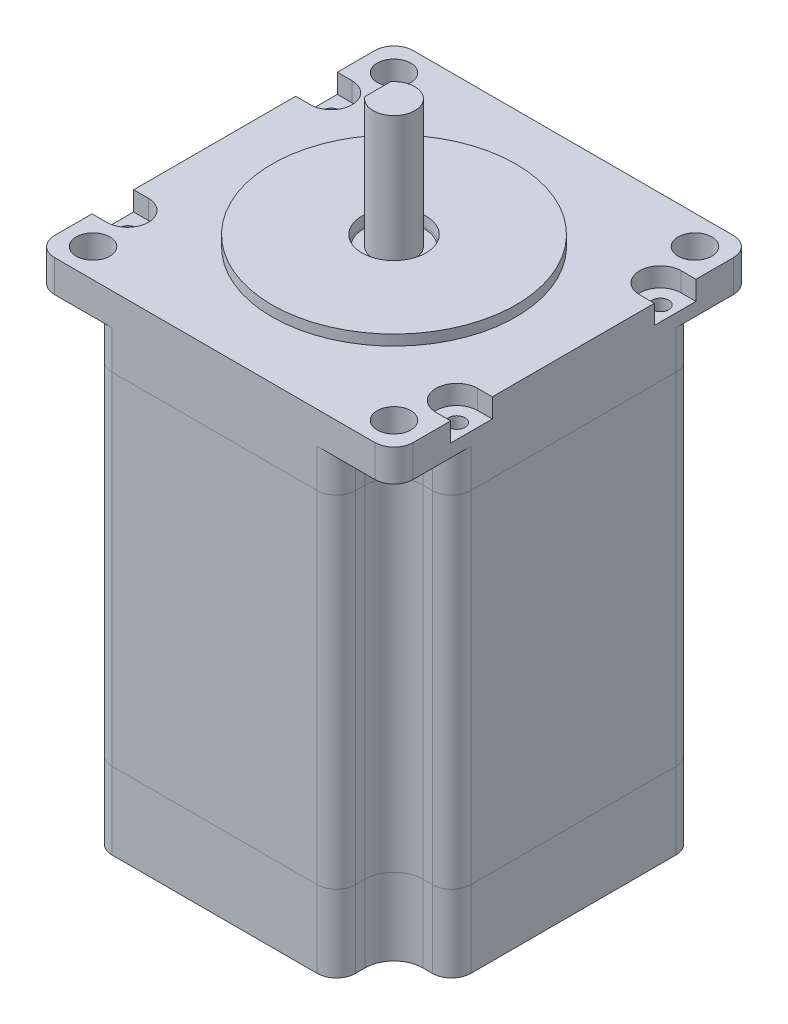
SolidWorks part; units mm, degrees
ref_plane "Front Plane" through (0, 0, 0) normal (0, 0, 1) x (1, 0, 0)
ref_plane "Top Plane" through (0, 0, 0) normal (0, 1, 0) x (1, 0, 0)
ref_plane "Right Plane" through (0, 0, 0) normal (1, 0, 0) x (0, 0, -1)
sketch "Sketch2" plane through (0, 0, 0) normal (0, 1, 0) x (1, 0, 0)
  line L0 (-28, 0) -> (28, 0) construction
  line L1 (0, -28) -> (0, 28) construction
  line L2 (-16, 28) -> (16, 28)
  line L3 (-28, -16) -> (-28, 16)
  line L4 (28, -16) -> (28, 16)
  line L5 (-16, -28) -> (16, -28)
  line L10 (-25, 19) -> (-23.4993, 19)
  line L11 (-19, 25) -> (-19, 23.4993)
  line L12 (-19, 23.4993) -> (-18.9317, 23.4767)
  line L13 (19, 25) -> (19, 23.4993)
  line L14 (25, 19) -> (23.4993, 19)
  line L15 (-19, -23.4993) -> (-18.9317, -23.4767)
  line L16 (-19, -25) -> (-19, -23.4993)
  line L17 (-25, -19) -> (-23.4993, -19)
  line L18 (25, -19) -> (23.4993, -19)
  line L19 (19, -25) -> (19, -23.4993)
  circle A0 centre (-25.7, 15.9) radius 1.3
  arc A1 (-19, 23.4993) -> (-23.4993, 19) centre (-23.4993, 23.4993) cw
  arc A2 (-28, 16) -> (-25, 19) centre (-25, 16) cw
  arc A3 (-16, 28) -> (-19, 25) centre (-16, 25) ccw
  arc A4 (16, 28) -> (19, 25) centre (16, 25) cw
  arc A5 (19, 23.4993) -> (23.4993, 19) centre (23.4993, 23.4993) ccw
  arc A6 (28, 16) -> (25, 19) centre (25, 16) ccw
  circle A7 centre (25.7, 15.9) radius 1.3
  arc A8 (-16, -28) -> (-19, -25) centre (-16, -25) cw
  arc A9 (-28, -16) -> (-25, -19) centre (-25, -16) ccw
  arc A10 (-19, -23.4993) -> (-23.4993, -19) centre (-23.4993, -23.4993) ccw
  circle A11 centre (-25.7, -15.9) radius 1.3
  circle A12 centre (25.7, -15.9) radius 1.3
  arc A13 (28, -16) -> (25, -19) centre (25, -16) cw
  arc A14 (19, -23.4993) -> (23.4993, -19) centre (23.4993, -23.4993) cw
  arc A15 (16, -28) -> (19, -25) centre (16, -25) ccw
  circle A16 centre (0, 0) radius 5
  point P3 (0, 0)
  point P6 (0, 0)
  point P9 (0, 28)
  point P12 (-28, 0)
  point P15 (28, 0)
  point P18 (0, -28)
  point P25 (-23.4993, 23.4993)
  dimension "D5" = 2.6
  dimension "D8" = 3
  dimension "D9" = 10
  dimension "D1" = 56
  dimension "D2" = 56
extrude "Boss-Extrude2" add sketch "Sketch2" along normal blind 12 contours L5 A15 L19 A14 L18 A13 L4 A6 L14 A5 L13 A4 L2 A3 L11 A1 L10 A2 L3 A9 L17 A10 L16 A8 A16 A11 A0 A7 A12 region at (0, 0, -27.208)
extrude "Boss-Extrude3" add sketch "Sketch2<5>" along normal blind 53.3 from surface separate body contours L5 A15 L19 A14 L18 A13 L4 A6 L14 A5 L13 A4 L2 A3 L11 A1 L10 A2 L3 A9 L17 A10 L16 A8 A16 A11 A0 A7 A12 region at (0, 0, -27.208) starting at face at (0, 12, 5)
sketch "Sketch2<5>" plane through (0, 0, 0) normal (0, 1, 0) x (1, 0, 0) same geometry as "Sketch2"
extrude "Boss-Extrude4" add sketch "Sketch2<6>" along normal blind 6 from surface separate body contours L5 A15 L19 A14 L18 A13 L4 A6 L14 A5 L13 A4 L2 A3 L11 A1 L10 A2 L3 A9 L17 A10 L16 A8 A16 A11 A0 A7 A12 region at (0, 0, -27.208) starting at face at (-25.7, 65.3, -14.6)
sketch "Sketch2<6>" plane through (0, 0, 0) normal (0, 1, 0) x (1, 0, 0) same geometry as "Sketch2"
ref_plane "Plane1" through (0, 71.3, 0) normal (0, 1, 0) x (1, 0, 0)
sketch "Sketch4" plane through (0, 71.3, 0) normal (0, 1, 0) x (1, 0, 0)
  line L0 (-28, 0) -> (28, 0) construction
  line L1 (0, -28) -> (0, 28) construction
  line L2 (-28, 28) -> (28, 28)
  line L3 (-28, -28) -> (-28, -19.15)
  line L4 (28, -28) -> (28, -19.15)
  line L5 (-28, -28) -> (28, -28)
  line L6 (25.7, 19.15) -> (28, 19.15)
  line L7 (25.7, 12.65) -> (28, 12.65)
  line L8 (-25.7, 19.15) -> (-28, 19.15)
  line L9 (-25.7, 12.65) -> (-28, 12.65)
  line L10 (28, 19.15) -> (28, 28)
  line L11 (25.7, -12.65) -> (28, -12.65)
  line L12 (25.7, -19.15) -> (28, -19.15)
  line L13 (-25.7, -19.15) -> (-28, -19.15)
  line L14 (-25.7, -12.65) -> (-28, -12.65)
  line L15 (-28, -12.65) -> (-28, 12.65)
  line L16 (28, -12.65) -> (28, 12.65)
  line L17 (-28, 19.15) -> (-28, 28)
  line L18 (-28, 19.15) -> (-28, 12.65)
  line L19 (-28, -12.65) -> (-28, -19.15)
  line L20 (28, -12.65) -> (28, -19.15)
  line L21 (28, 19.15) -> (28, 12.65)
  circle A0 centre (-25.7, 15.9) radius 1.3
  arc A1 (25.7, 19.15) -> (25.7, 12.65) centre (25.7, 15.9) ccw
  circle A2 centre (-23.4993, 23.4993) radius 2.625
  circle A3 centre (23.4993, 23.4993) radius 2.625
  circle A4 centre (-23.4993, -23.4993) radius 2.625
  circle A5 centre (23.4993, -23.4993) radius 2.625
  arc A6 (-25.7, 19.15) -> (-25.7, 12.65) centre (-25.7, 15.9) cw
  arc A7 (25.7, -19.15) -> (25.7, -12.65) centre (25.7, -15.9) cw
  arc A8 (-25.7, -19.15) -> (-25.7, -12.65) centre (-25.7, -15.9) ccw
  circle A9 centre (25.7, 15.9) radius 1.3
  circle A10 centre (25.7, -15.9) radius 1.3
  circle A11 centre (-25.7, -15.9) radius 1.3
  circle A16 centre (0, 0) radius 5
  point P2 (0, 0)
  point P5 (0, 0)
  point P8 (0, 28)
  point P11 (-28, 0)
  point P14 (28, 0)
  point P17 (0, -28)
  point P21 (-23.4993, 23.4993)
  dimension "D4" = 6.5
  dimension "D5" = 10
  dimension "D6" = 5.25
  dimension "D7" = 5.25
  dimension "D8" = 5.25
  dimension "D9" = 5.25
  dimension "D1" = 56
  dimension "D2" = 56
extrude "Boss-Extrude5" add sketch "Sketch4" along normal blind 5 contours A6 L8 L18 L9 | L6 A1 L7 L21 | A8 L13 L3 L5 L4 L12 A7 L11 L16 L7 A1 L6 L10 L2 L17 L8 A6 L9 L15 L14 A16 A5 A4 A3 A2 | L13 A8 L14 L19 | A7 L12 L20 L11 region at (0, 71.3, -27.208) region at (-26.85, 71.3, -19.0645) region at (27.9145, 71.3, -15.9) region at (-26.85, 71.3, 12.7355) region at (27.9145, 71.3, 15.9)
sketch "Sketch5" plane through (0, 71.3, 0) normal (0, 1, 0) x (1, 0, 0)
  line L0 (-28, 19.15) -> (-28, 12.65)
  line L1 (-28, 12.65) -> (-25.7, 12.65)
  line L2 (-25.7, 19.15) -> (-28, 19.15)
  line L3 (0, 28) -> (0, -28) construction
  line L4 (-28, 0) -> (28, 0) construction
  line L5 (25.7, 19.15) -> (28, 19.15)
  line L6 (28, 12.65) -> (25.7, 12.65)
  line L7 (28, 19.15) -> (28, 12.65)
  line L8 (28, -19.15) -> (28, -12.65)
  line L9 (28, -12.65) -> (25.7, -12.65)
  line L10 (25.7, -19.15) -> (28, -19.15)
  line L11 (-25.7, -19.15) -> (-28, -19.15)
  line L12 (-28, -12.65) -> (-25.7, -12.65)
  line L13 (-28, -19.15) -> (-28, -12.65)
  arc A0 (-25.7, 12.65) -> (-25.7, 19.15) centre (-25.7, 15.9) ccw
  arc A1 (25.7, 12.65) -> (25.7, 19.15) centre (25.7, 15.9) cw
  arc A2 (25.7, -12.65) -> (25.7, -19.15) centre (25.7, -15.9) ccw
  arc A3 (-25.7, -12.65) -> (-25.7, -19.15) centre (-25.7, -15.9) cw
extrude "Cut-Extrude1" cut sketch "Sketch5" against normal blind 3 from surface starting at face at (0, 76.3, 0)
ref_plane "Plane2" through (0, 76.3, 0) normal (0, 1, 0) x (1, 0, 0)
sketch "Sketch6" plane through (0, 76.3, 0) normal (0, 1, 0) x (1, 0, 0)
  line L1 (-2.55, -2.0149) -> (-2.55, 2.0149)
  arc A0 (-2.55, -2.0149) -> (-2.55, 2.0149) centre (0, 0) ccw
  point P8 (-2.55, 0)
  dimension "D1" = 6.5
  dimension "D2" = 4.0299
extrude "Boss-Extrude6" add sketch "Sketch6" along normal blind 20 separate body
sketch "Sketch7" plane through (0, 76.3, 0) normal (0, 1, 0) x (1, 0, 0)
  circle A0 centre (0, 0) radius 4.75
  dimension "D1" = 9.5
extrude "Boss-Extrude7" add sketch "Sketch7" against normal blind 74 separate body
sketch "Sketch8" plane through (0, 76.3, 0) normal (0, 1, 0) x (1, 0, 0)
  circle A0 centre (0, 0) radius 19.05
  circle A1 centre (0, 0) radius 5
  dimension "D1" = 38.1
extrude "Boss-Extrude8" add sketch "Sketch8" along normal blind 1.63 separate body
fillet "Fillet1" radius 3 4 edges at (-28, 73.8, -28) (28, 73.8, -28) (28, 73.8, 28) (-28, 73.8, 28)
